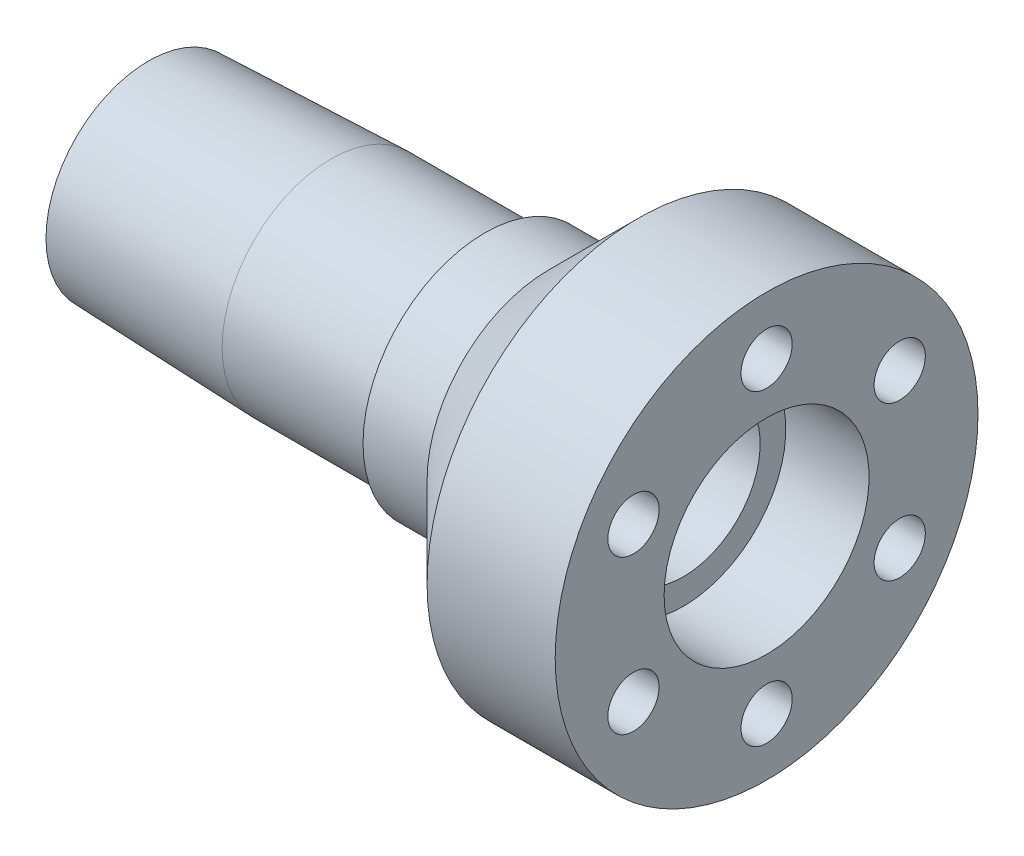
SolidWorks part; units mm, degrees
ref_plane "Front Plane" through (0, 0, 0) normal (0, 0, 1) x (1, 0, 0)
ref_plane "Top Plane" through (0, 0, 0) normal (0, 1, 0) x (1, 0, 0)
ref_plane "Right Plane" through (0, 0, 0) normal (1, 0, 0) x (0, 0, -1)
sketch "Sketch2" plane through (0, 0, 0) normal (0, 0, 1) x (1, 0, 0)
  line L0 (0, 0) -> (64.6823, 0) construction
  line L1 (0, 8) -> (0, 6)
  line L2 (0, 6) -> (41.75, 6)
  line L7 (48.25, 8) -> (48.25, 16.5024)
  line L8 (48.25, 16.5024) -> (38.25, 16.5024)
  line L11 (41.75, 6) -> (41.75, 8)
  line L12 (41.75, 8) -> (48.25, 8)
  line L15 (31.2476, 9.5) -> (38.25, 16.5024)
  line L16 (0, 8) -> (14.2476, 8.5)
  line L17 (14.2476, 8.5) -> (26.2476, 8.5)
  line L19 (26.2476, 8.5) -> (26.2476, 9.5)
  line L20 (26.2476, 9.5) -> (31.2476, 9.5)
  dimension "D1" = 8.5
  dimension "D2" = 6
  dimension "D3" = 8
  dimension "D4" = 6.5
  dimension "D5" = 1
  dimension "D6" = 45
  dimension "D7" = 10
  dimension "D8" = 41.75
  dimension "D9" = 12
  dimension "D10" = 8.5024
  dimension "D11" = 8
  dimension "D12" = 5
revolve "Revolve1" add sketch "Sketch2" angle 360 about L0
sketch "Sketch7" plane through (48.25, 0, 0) normal (1, 0, 0) x (0, 0, -1)
  line L0 (0, -16.5024) -> (0, 16.5024) construction
  circle A0 centre (0, 12) radius 2
  circle A1 centre (0, 0) radius 16.5024 construction
  circle A3 centre (10.3923, 6) radius 2
  circle A4 centre (10.3923, -6) radius 2
  circle A5 centre (0, -12) radius 2
  circle A6 centre (-10.3923, -6) radius 2
  circle A7 centre (-10.3923, 6) radius 2
  point P20 (0, 0)
  dimension "D1" = 4
  dimension "D2" = 12
  dimension "D3" = 6
extrude "Cut-Extrude2" cut sketch "Sketch7" against normal blind 8
